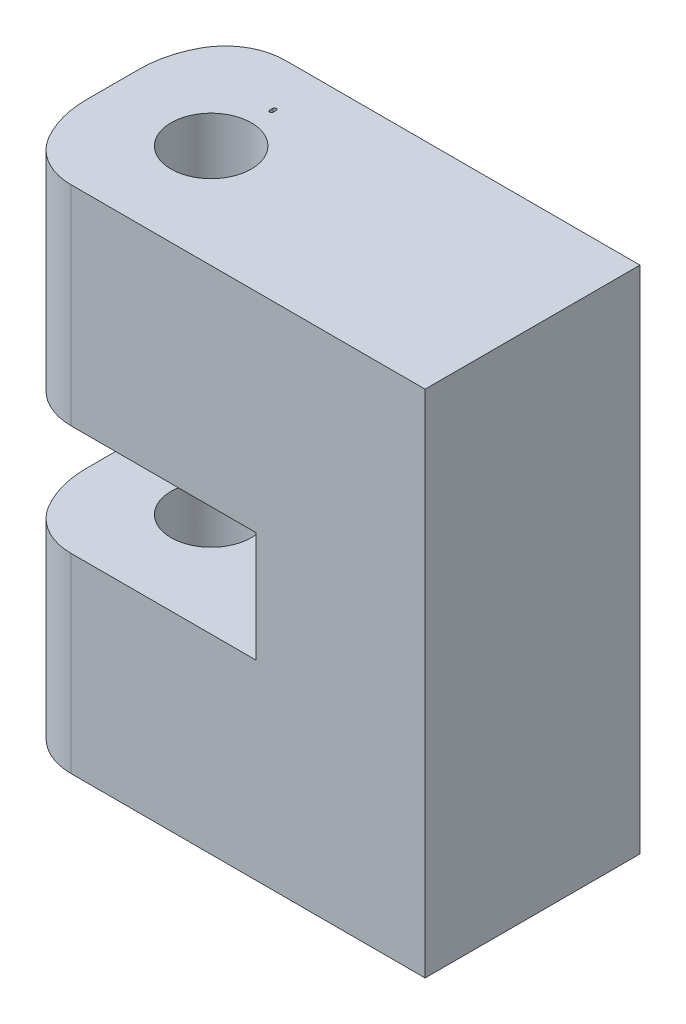
SolidWorks part; units mm, degrees
ref_plane "Front" through (0, 0, 0) normal (0, 0, 1) x (1, 0, 0)
ref_plane "Top" through (0, 0, 0) normal (0, 1, 0) x (1, 0, 0)
ref_plane "Right" through (0, 0, 0) normal (1, 0, 0) x (0, 0, -1)
sketch "Sketch1" plane through (0, 0, 0) normal (0, 1, 0) x (1, 0, 0)
  line L0 (0, 9.3172) -> (0, 9.1678) construction
  line L1 (0, 0) -> (20.32, 0)
  line L2 (0, 0) -> (0, 12.7)
  line L3 (0, 12.7) -> (20.32, 12.7)
  line L4 (20.32, 0) -> (20.32, 12.7)
  line L5 (0.0894, 9.3172) -> (0.0894, 9.1678)
  line L6 (-0.0894, 9.3172) -> (-0.0894, 9.1678)
  line L7 (0, 7.6957) -> (0, 5.0493) construction
  line L10 (5.1, 7.6957) -> (5.1, 5.0493)
  line L11 (-5.1, 7.6957) -> (-5.1, 5.0493)
  arc A0 (0.0894, 9.3172) -> (-0.0894, 9.3172) centre (0, 9.3172) ccw
  arc A1 (-0.0894, 9.1678) -> (0.0894, 9.1678) centre (0, 9.1678) ccw
  arc A4 (5.1, 7.6957) -> (-5.1, 7.6957) centre (0, 7.6957) ccw
  arc A5 (-5.1, 5.0493) -> (5.1, 5.0493) centre (0, 5.0493) ccw
  point P7 (0, 9.2425)
  point P14 (0, 6.3725)
  dimension "D1" = 20.32
  dimension "D2" = 12.7
extrude "Boss-Extrude4" add sketch "Sketch1" along normal blind 25.4 contours L11 A5 L1 L2 A1 L6 A0 L3 A4 | L1 A5 L10 A4 L3 L2 A0 L5 A1 | A5 L1 L4 L3 A4 L10 region at (2.2644, 0, -6.3666) region at (-2.2571, 0, -6.3757) region at (12.2627, 0, -6.3452)
sketch "Sketch3" plane through (0, 25.4, 0) normal (0, 1, 0) x (1, 0, 0)
  circle A0 centre (0, 6.1634) radius 2
  dimension "D1" = 4
extrude "Cut-Extrude1" cut sketch "Sketch3" against normal blind 25.4 contours A0
sketch "Sketch5" plane through (20.32, 0, 0) normal (1, 0, 0) x (0, 0, -1)
  line L1 (38.2751, 38.8271) -> (-16.024, 38.8271)
  line L2 (38.2751, 38.8271) -> (38.2751, -55.3885)
  line L3 (38.2751, -55.3885) -> (-16.024, -55.3885)
  line L4 (-16.024, 38.8271) -> (-16.024, -55.3885)
extrude "Cut-Extrude2" cut sketch "Sketch5" against normal blind 4.5
sketch "Sketch7" plane through (-5.1, 0, 0) normal (-1, 0, 0) x (0, 0, 1)
  line L0 (-7.6957, 25.4) -> (-5.0493, 25.4) construction
  line L1 (-15.6651, 15) -> (3.0281, 15)
  line L2 (-15.6651, 15) -> (-15.6651, 9.5)
  line L3 (-15.6651, 9.5) -> (3.0281, 9.5)
  line L4 (3.0281, 15) -> (3.0281, 9.5)
  dimension "D1" = 5.5
  dimension "D2" = 10.4
extrude "Cut-Extrude3" cut sketch "Sketch7" against normal blind 14.5
sketch "Sketch9" plane through (0, 0, -12.7) normal (0, 0, -1) x (-1, 0, 0)
  line L1 (-22.5674, 28.7595) -> (13.5442, 28.7595)
  line L2 (-22.5674, 28.7595) -> (-22.5674, -4.4046)
  line L3 (-22.5674, -4.4046) -> (13.5442, -4.4046)
  line L4 (13.5442, 28.7595) -> (13.5442, -4.4046)
extrude "Cut-Extrude4" cut sketch "Sketch9" against normal blind 1
sketch "Sketch10" plane through (0, 0, 0) normal (0, 0, 1) x (1, 0, 0)
  line L1 (-28.2632, -7.6451) -> (34.5285, -7.6451)
  line L2 (-28.2632, -7.6451) -> (-28.2632, 29.5981)
  line L3 (-28.2632, 29.5981) -> (34.5285, 29.5981)
  line L4 (34.5285, -7.6451) -> (34.5285, 29.5981)
extrude "Cut-Extrude6" cut sketch "Sketch10" against normal blind 1
fillet "Fillet2" radius 3 4 edges at (-3.1005, 4.75, -1) (-3.1005, 20.2, -1) (-3.1585, 20.2, -11.7) (-3.1585, 4.75, -11.7)
sketch "Sketch11" plane through (9.4, 0, 0) normal (-1, 0, 0) x (0, 0, 1)
  line L1 (-11.7, 9.5) -> (-1, 9.5)
  line L2 (-11.7, 9.5) -> (-11.7, 15)
  line L3 (-11.7, 15) -> (-1, 15)
  line L4 (-1, 9.5) -> (-1, 15)
extrude "Boss-Extrude5" add sketch "Sketch11" along normal blind 2
